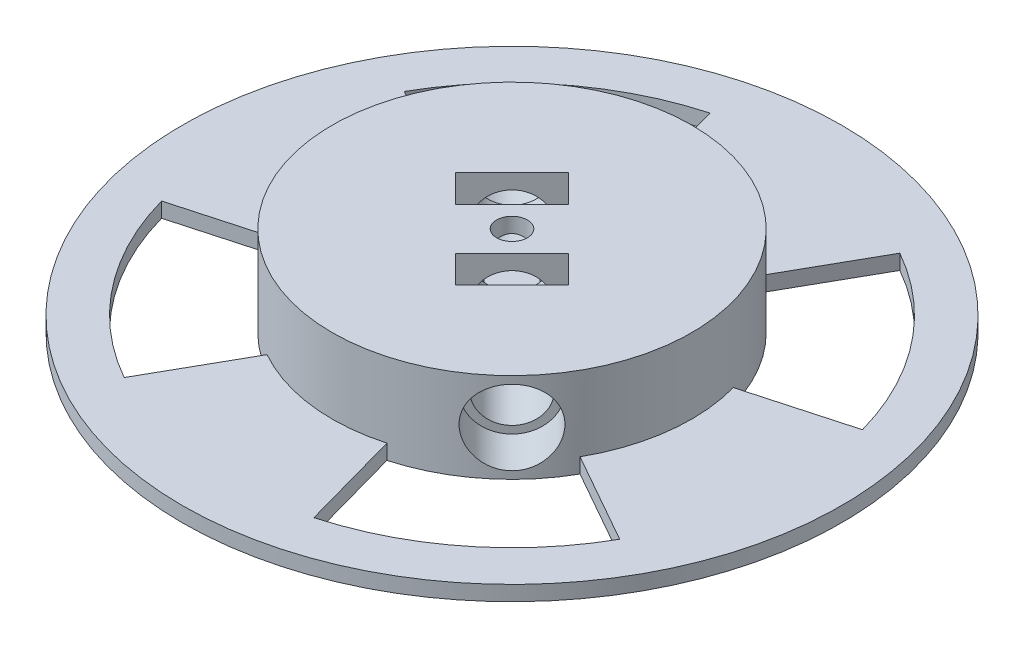
SolidWorks part; units mm, degrees
ref_plane "Alzado" through (0, 0, 0) normal (0, 0, 1) x (1, 0, 0)
ref_plane "Planta" through (0, 0, 0) normal (0, 1, 0) x (1, 0, 0)
ref_plane "Vista lateral" through (0, 0, 0) normal (1, 0, 0) x (0, 0, -1)
sketch "Croquis1" plane through (0, 0, 0) normal (0, 1, 0) x (1, 0, 0)
  line L0 (0, 0) -> (22, 0) construction
  line L1 (0, 0) -> (0, 22) construction
  line L2 (0, 0) -> (0, -22) construction
  line L3 (0, 0) -> (-22, 0) construction
  line L4 (0, 0) -> (0, 22)
  line L5 (0, 0) -> (22, 0)
  line L6 (0, 0) -> (0, -22)
  line L7 (0, 0) -> (-22, 0)
  circle A0 centre (0, 0) radius 22
  circle A1 centre (0, 0) radius 12
  circle A2 centre (0, 0) radius 19
  dimension "D1" = 44
  dimension "D2" = 3
  dimension "D3" = 24
extrude "Saliente-Extruir4" add sketch "Croquis1" along normal blind 6 contours L7 A1 L6 | L4 A1 L7 | L5 A1 L4 | L6 A1 L5 region at (-5.093, 0, -5.093) region at (5.093, 0, -5.093) region at (5.093, 0, 5.093) region at (-5.093, 0, 5.093)
sketch "Croquis10" plane through (0, 0, 0) normal (0, 1, 0) x (1, 0, 0)
  circle A0 centre (0, 0) radius 1.03
  dimension "D1" = 2.06
extrude "Saliente-Extruir5" add sketch "Croquis10" along normal blind 3
extrude "Cortar-Extruir7" cut sketch "Croquis10<3>" along normal blind 6
sketch "Croquis10<3>" plane through (0, 0, 0) normal (0, 1, 0) x (1, 0, 0) same geometry as "Croquis10"
ref_plane "Plano1" through (0, 0, 0) normal (0.7071, 0, 0.7071) x (0.7071, 0, -0.7071)
sketch "Croquis11" plane through (0, 0, 0) normal (0.7071, 0, 0.7071) x (0.7071, 0, -0.7071)
  line L1 (0, 6) -> (0, 0) construction
  circle A0 centre (0, 3) radius 2
  circle A1 centre (0, 3) radius 2.5
  dimension "D1" = 4
  dimension "D2" = 5
extrude "Cortar-Extruir8" cut sketch "Croquis11" along normal up to next contours A0
sketch "Croquis14" plane through (0, 0, 0) normal (0.7071, 0, 0.7071) x (0.7071, 0, -0.7071)
  line L0 (0, 6) -> (0, 0) construction
  line L4 (1.3279, 5.3) -> (-1.3279, 5.3)
  line L5 (-1.3279, 5.3) -> (-2.6558, 3)
  line L6 (-2.6558, 3) -> (-1.3279, 0.7)
  line L7 (-1.3279, 0.7) -> (1.3279, 0.7)
  line L8 (1.3279, 0.7) -> (2.6558, 3)
  line L9 (2.6558, 3) -> (1.3279, 5.3)
  circle A0 centre (0, 3) radius 2.3 construction
  dimension "D1" = 4.6
extrude "Cortar-Extruir11" cut sketch "Croquis11<3>" along normal through all from offset 9 contours A1
sketch "Croquis11<3>" plane through (0, 0, 0) normal (0.7071, 0, 0.7071) x (0.7071, 0, -0.7071) same geometry as "Croquis11"
extrude "Cortar-Extruir9" cut sketch "Croquis14" against normal blind 2.6 from offset 4.6
extrude "Cortar-Extruir12" cut sketch "Croquis11<4>" against normal up to next contours L1 A0 | A0 L1 region at (0.6002, 3, -0.6002) region at (-0.6002, 3, 0.6002)
sketch "Croquis11<4>" plane through (0, 0, 0) normal (0.7071, 0, 0.7071) x (0.7071, 0, -0.7071) same geometry as "Croquis11"
sketch "Croquis16" plane through (0, 6, 0) normal (0, 1, 0) x (1, 0, 0)
  line L0 (-0.4637, -3.2922) -> (1.3747, -5.1306) construction
  line L1 (3.2922, 0.4637) -> (5.1306, -1.3747) construction
  line L2 (-0.4637, -3.2922) -> (1.3747, -5.1306)
  line L3 (3.2922, 0.4637) -> (5.1306, -1.3747)
  line L4 (-0.4637, -3.2922) -> (3.2922, 0.4637)
  line L5 (5.1306, -1.3747) -> (1.3747, -5.1306)
extrude "Cortar-Extruir10" cut sketch "Croquis16" against normal up to vertex (3 mm away) up to point (-0.4637, 3, 3.2922)
extrude "Cortar-Extruir13" cut sketch "Croquis11<5>" against normal through all from offset 9 contours A1 offset against normal yes
sketch "Croquis11<5>" plane through (0, 0, 0) normal (0.7071, 0, 0.7071) x (0.7071, 0, -0.7071) same geometry as "Croquis11"
extrude "Cortar-Extruir14" cut sketch "Croquis14<2>" against normal blind 2.6 from offset 2 offset against normal yes
sketch "Croquis14<2>" plane through (0, 0, 0) normal (0.7071, 0, 0.7071) x (0.7071, 0, -0.7071) same geometry as "Croquis14"
sketch "Croquis18" plane through (0, 6, 0) normal (0, 1, 0) x (1, 0, 0)
  line L0 (15.5563, 15.5563) -> (-15.5563, -15.5563) construction
  line L1 (-38.8909, -38.8909) -> (38.8909, 38.8909) construction
  line L2 (-15.5563, -15.5563) -> (-38.8909, -38.8909) construction
  line L7 (5.1306, -1.3747) -> (3.2922, 0.4637)
  line L8 (3.2922, 0.4637) -> (-0.4637, -3.2922)
  line L9 (1.3747, -5.1306) -> (5.1306, -1.3747)
  line L10 (-0.4637, -3.2922) -> (1.3747, -5.1306)
  line L11 (-3.2922, -0.4637) -> (-5.1306, 1.3747)
  line L12 (-5.1306, 1.3747) -> (-1.3747, 5.1306)
  line L13 (-1.3747, 5.1306) -> (0.4637, 3.2922)
  line L14 (0.4637, 3.2922) -> (-3.2922, -0.4637)
extrude "Cortar-Extruir15" cut sketch "Croquis18" against normal up to vertex (3 mm away) contours L14 L13 L12 L11 region at (-2.3335, 6, -2.3335) up to point (5.1306, 3, 1.3747)
extrude "Saliente-Extruir6" add sketch "Croquis1<11>" along normal blind 1 contours L5 A2 L4 A1 | A2 L5 A0 L4 | A2 L7 A0 L6 | L7 A2 L6 A1 | A2 L6 A0 L5 | A2 L4 A0 L7 | L6 A2 L5 A1 | L4 A2 L7 A1 region at (-10.0353, 0, -10.0353) region at (10.0353, 0, -10.0353) region at (10.0353, 0, 10.0353) region at (-10.0353, 0, 10.0353) region at (-13.655, 0, -13.655) region at (0.3111, 0, -20.5) region at (20.5, 0, 0.3111) region at (-0.3111, 0, 20.5)
sketch "Croquis1<11>" plane through (0, 0, 0) normal (0, 1, 0) x (1, 0, 0) same geometry as "Croquis1"
sketch "Croquis20" plane through (0, 0, 0) normal (0, -1, 0) x (1, 0, 0)
  line L0 (-8.1317, -4.5962) -> (-4.5962, -8.1317) construction
  line L1 (-8.1317, -4.5962) -> (-4.5962, -8.1317)
  line L2 (8.1317, 4.5962) -> (4.5962, 8.1317) construction
  line L3 (8.1317, 4.5962) -> (4.5962, 8.1317)
  line L4 (0, 0) -> (16.5407, 9.3491)
  line L5 (0, 0) -> (18.3068, -5.0852)
  line L6 (0, 0) -> (9.3491, -16.5407)
  line L7 (0, 0) -> (-5.0852, -18.3068)
  line L8 (0, 0) -> (-16.5407, -9.3491)
  line L9 (0, 0) -> (-18.3068, 5.0852)
  line L10 (0, 0) -> (-9.3491, 16.5407)
  line L11 (0, 0) -> (5.0852, 18.3068)
  circle A0 centre (0, 0) radius 12 construction
  circle A1 centre (0, 0) radius 12
  circle A2 centre (0, 0) radius 19
  circle A3 centre (0, 0) radius 22 construction
  point P21 (0, 0)
  dimension "D1" = 3
  dimension "D2" = 8
extrude "Cortar-Extruir17" cut sketch "Croquis20" against normal blind 2 contours L4 A2 L11 A1 | L6 A2 L5 A1 | L8 A2 L7 A1 | L10 A2 L9 A1 region at (12.101, 0, -9.4625) region at (-9.4625, 0, -12.101) region at (-12.101, 0, 9.4625) region at (9.4625, 0, 12.101)
